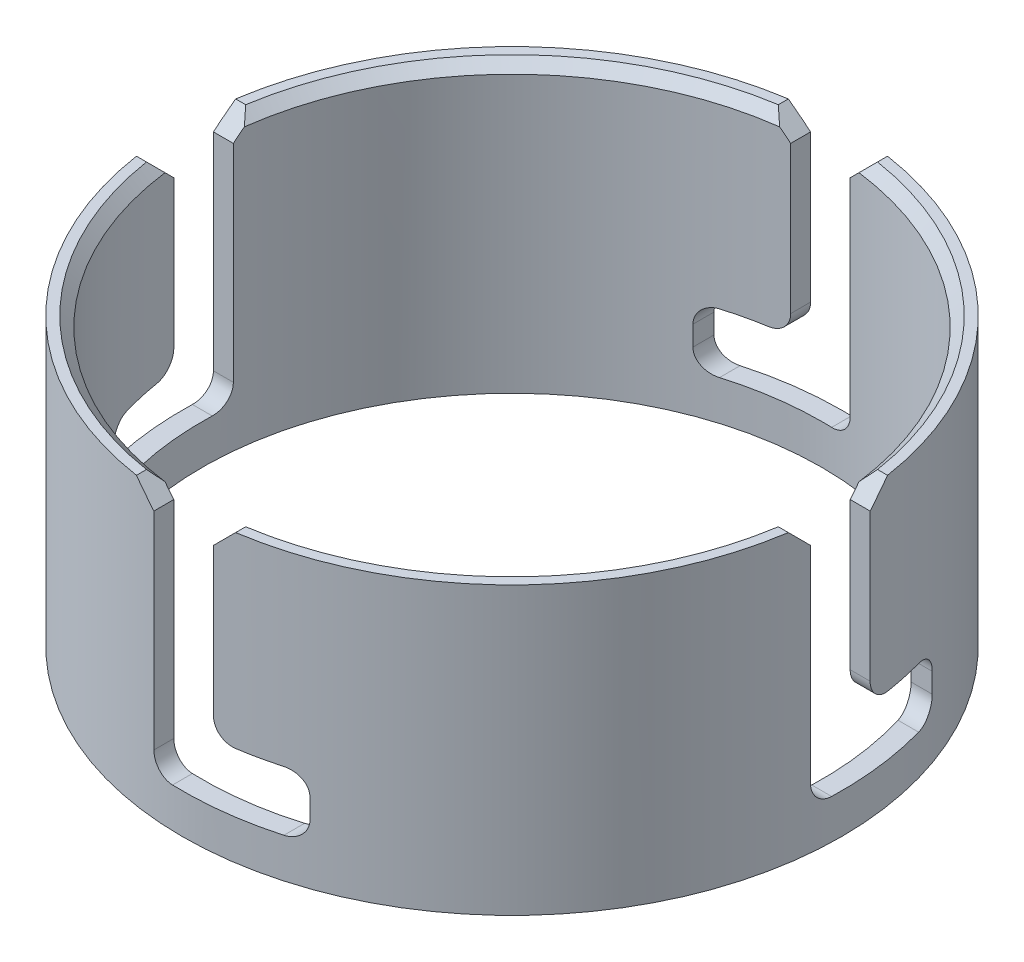
SolidWorks part; units mm, degrees
material "Plain Carbon Steel"
ref_plane "Front Plane" through (0, 0, 0) normal (0, 0, 1) x (1, 0, 0)
ref_plane "Top Plane" through (0, 0, 0) normal (0, 1, 0) x (1, 0, 0)
ref_plane "Right Plane" through (0, 0, 0) normal (1, 0, 0) x (0, 0, -1)
sketch "Sketch2" plane through (0, 0, 0) normal (1, 0, 0) x (0, 0, -1)
  line L0 (-78.0999, 0) -> (-83.0999, 0)
  line L1 (-83.0999, 0) -> (-83.0999, 72.15)
  line L2 (-83.0999, 72.15) -> (-78.0999, 72.15)
  line L5 (-78.0999, 72.15) -> (-78.0999, 0)
  dimension "D1" = 83.0999
  dimension "D2" = 72.15
  dimension "D3" = 5
ref_axis "Axis1" through (0, -3.6075, 0) along (0, 1, 0)
revolve "Revolve1" add sketch "Sketch2" angle 360 about axis through (0, -3.6075, 0) along (0, 1, 0)
sketch "Sketch3" plane through (0, 0, 0) normal (1, 0, 0) x (0, 0, -1)
  line L0 (-7.5, 72.15) -> (7.5, 72.15)
  line L1 (83.0999, 72.15) -> (-83.0999, 72.15) construction
  line L2 (7.5, 72.15) -> (7.5, 10)
  line L3 (7.5, 10) -> (-27.5, 10)
  line L4 (-27.5, 10) -> (-27.5, 25)
  line L5 (-27.5, 25) -> (-7.5, 25)
  line L6 (-7.5, 25) -> (-7.5, 72.15)
  line L7 (0, -3.6075) -> (0, 75.7575) construction
  line L8 (0, 0) -> (0, 47.5309) construction
  line L9 (-83.0999, 0) -> (83.0999, 0) construction
  dimension "D1" = 10
  dimension "D2" = 15
  dimension "D3" = 15
  dimension "D4" = 20
extrude "Cut-Extrude1" cut sketch "Sketch3" against normal through all
fillet "Fillet1" radius 5 2 edges at (-80.2499, 25, 7.5) (-80.2499, 10, -7.5)
chamfer "Chamfer1" distance 5 angle 45 2 edges at (-80.2499, 72.15, 7.5) (-80.2499, 72.15, -7.5)
fillet "Fillet3" radius 5 2 edges at (-75.758, 25, 27.5) (-75.758, 10, 27.5)
pattern_circular "CirPattern1" count 4 over 360 about axis through (0, -3.6075, 0) along (0, 1, 0) of "Fillet3", "Chamfer1", "Fillet1", "Cut-Extrude1"
chamfer "Chamfer2" distance 2.5 angle 45 4 edges at (-55.225, 72.15, -55.225) (55.225, 72.15, -55.225) (55.225, 72.15, 55.225) (-55.225, 72.15, 55.225)
equation "\"TubeDiameter\" = 6.5433in"
equation "\"D1@Sketch2\"=\"TubeDiameter\"/2"
